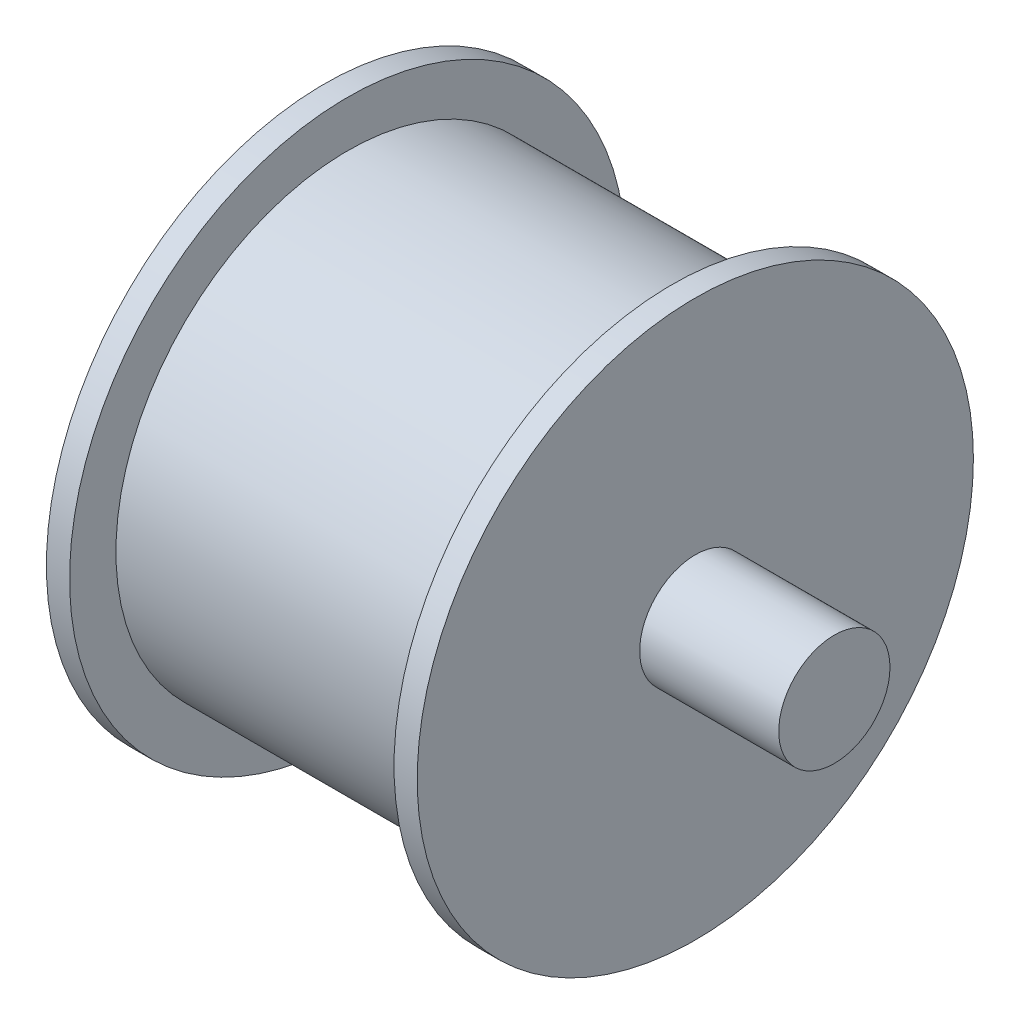
SolidWorks part; units mm, degrees
note: The reader was unsure of these and kept them because the rebuilt part matched: shared geometry of "Sketch4<3>".
ref_plane "Front Plane" through (0, 0, 0) normal (0, 0, 1) x (1, 0, 0)
ref_plane "Top Plane" through (0, 0, 0) normal (0, 1, 0) x (1, 0, 0)
ref_plane "Right Plane" through (0, 0, 0) normal (1, 0, 0) x (0, 0, -1)
sketch "Sketch3" plane through (0, 0, 0) normal (1, 0, 0) x (0, 0, -1)
  circle A0 centre (0, 0) radius 6
  dimension "D1" = 12
extrude "Boss-Extrude1" add sketch "Sketch3" against normal blind 15
sketch "Sketch4" plane through (0, 0, 0) normal (1, 0, 0) x (0, 0, -1)
  circle A0 centre (0, 0) radius 30
  circle A2 centre (0, 0) radius 25
  dimension "D1" = 60
  dimension "D2" = 5
extrude "Boss-Extrude2" add sketch "Sketch4" along normal blind 2.5 contours A0
extrude "Boss-Extrude3" add sketch "Sketch4<3>" along normal blind 17.5 from offset 2.5 contours A2
sketch "Sketch4<3>" plane through (0, 0, 0) normal (1, 0, 0) x (0, 0, -1) same geometry as "Sketch4"
mirror "Mirror1" about plane through (20, 0, 0) normal (1, 0, 0) of "Boss-Extrude3"
ref_plane "Plane1" through (20, 0, 0) normal (1, 0, 0) x (0, 0, -1)
mirror "Mirror2" about plane through (20, 0, 0) normal (1, 0, 0) of "Boss-Extrude2", "Boss-Extrude1"
mirror "Mirror3" about plane through (20, 0, 0) normal (1, 0, 0) of "Boss-Extrude1"
